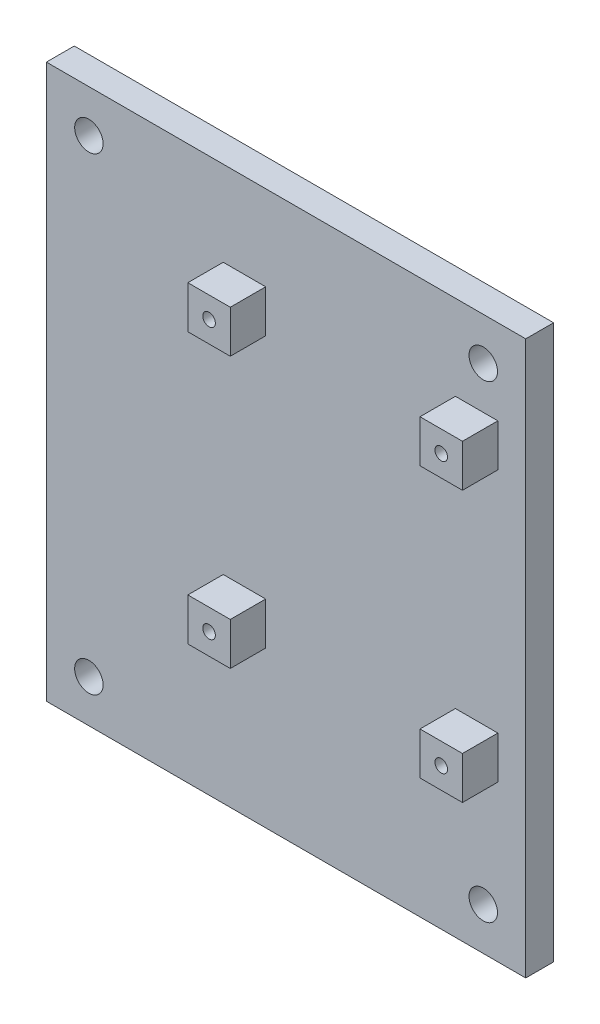
SolidWorks part; units mm, degrees
ref_plane "Front Plane" through (0, 0, 0) normal (0, 0, 1) x (1, 0, 0)
ref_plane "Top Plane" through (0, 0, 0) normal (0, 1, 0) x (1, 0, 0)
ref_plane "Right Plane" through (0, 0, 0) normal (1, 0, 0) x (0, 0, -1)
sketch "Sketch1" plane through (0, 0, 0) normal (0, 0, 1) x (1, 0, 0)
  line L1 (-43, -49.657) -> (43, -49.657)
  line L2 (-43, -49.657) -> (-43, 49.657)
  line L3 (-43, 49.657) -> (43, 49.657)
  line L4 (43, -49.657) -> (43, 49.657)
  line L5 (-43, -49.657) -> (43, 49.657) construction
  line L6 (-43, 49.657) -> (43, -49.657) construction
  point P0 (0, 0)
  dimension "D1" = 86
  dimension "D2" = 99.314
extrude "Boss-Extrude1" add sketch "Sketch1" along normal blind 5
sketch "Sketch2" plane through (0, 0, 5) normal (0, 0, 1) x (1, 0, 0)
  line L0 (43, 49.657) -> (-43, 49.657) construction
  line L1 (-11.276, 34.417) -> (-3.656, 34.417)
  line L2 (-11.276, 34.417) -> (-11.276, 26.797)
  line L3 (-11.276, 26.797) -> (-3.656, 26.797)
  line L4 (-3.656, 34.417) -> (-3.656, 26.797)
  line L5 (30.38, 34.417) -> (38, 34.417)
  line L6 (30.38, 34.417) -> (30.38, 26.797)
  line L7 (30.38, 26.797) -> (38, 26.797)
  line L8 (38, 34.417) -> (38, 26.797)
  line L9 (-11.276, -14.097) -> (-3.656, -14.097)
  line L10 (-11.276, -14.097) -> (-11.276, -21.717)
  line L11 (-11.276, -21.717) -> (-3.656, -21.717)
  line L12 (-3.656, -14.097) -> (-3.656, -21.717)
  line L13 (30.38, -14.097) -> (38, -14.097)
  line L14 (30.38, -14.097) -> (30.38, -21.717)
  line L15 (30.38, -21.717) -> (38, -21.717)
  line L16 (38, -14.097) -> (38, -21.717)
  line L18 (43, -49.657) -> (43, 49.657) construction
  dimension "D1" = 7.62
  dimension "D2" = 15.24
  dimension "D3" = 5
  dimension "D4" = 49.276
  dimension "D5" = 56.134
extrude "Boss-Extrude2" add sketch "Sketch2" along normal blind 6.35
hole_wizard "#4-40 Tapped Hole1" positions "Sketch3" profile "Sketch4" tap size "#4-40" standard "ANSI Inch"
sketch "Sketch3" plane through (0, 0, 11.35) normal (0, 0, 1) x (1, 0, 0)
  line L0 (-3.656, 34.417) -> (-11.276, 34.417) construction
  line L1 (-11.276, 34.417) -> (-11.276, 26.797) construction
  line L2 (38, 34.417) -> (30.38, 34.417) construction
  line L3 (30.38, 34.417) -> (30.38, 26.797) construction
  line L4 (-3.656, -14.097) -> (-11.276, -14.097) construction
  line L5 (-11.276, -14.097) -> (-11.276, -21.717) construction
  line L6 (38, -14.097) -> (30.38, -14.097) construction
  line L7 (30.38, -14.097) -> (30.38, -21.717) construction
  point P0 (-7.466, 30.607)
  point P2 (34.19, 30.607)
  point P4 (-7.466, -17.907)
  point P6 (34.19, -17.907)
  point P12 (-7.466, 34.417)
  point P16 (-11.276, 30.607)
  point P20 (34.19, 34.417)
  point P24 (30.38, 30.607)
  point P28 (-7.466, -14.097)
  point P32 (-11.276, -17.907)
  point P36 (34.19, -14.097)
  point P40 (30.38, -17.907)
sketch "Sketch4" plane through (-7.466, 30.607, 11.35) normal (1, 0, 0) x (0, -1, 0)
  line L0 (0, 0) -> (0, 5.429)
  line L1 (0, 5.429) -> (1.1303, 4.7498)
  line L2 (1.1303, 4.7498) -> (1.1303, 0)
  line L5 (1.1303, 0) -> (0, 0)
  line L10 (0, 5.429) -> (-1.1303, 4.7498) construction
  line L11 (0, -6.35) -> (0, 107.95) construction
  dimension "Tap Drill Dia." = 2.2606
  dimension "Tap Drill Depth" = 4.7498
  dimension "Drill Angle" = 118
cosmetic thread "Hole Thread1" parameters "D1"=5.588, "D2"=2.8448
cosmetic thread "Hole Thread2" parameters "D1"=5.588, "D2"=2.8448
cosmetic thread "Hole Thread3" parameters "D1"=5.588, "D2"=2.8448
cosmetic thread "Hole Thread4" parameters "D1"=5.588, "D2"=2.8448
hole_wizard "#10 Clearance Hole1" positions "Sketch5" profile "Sketch6" hole size "#10" standard "ANSI Inch" end condition through all
sketch "Sketch5" plane through (0, 0, 5) normal (0, 0, 1) x (1, 0, 0)
  line L0 (-43, 49.657) -> (-43, -49.657) construction
  line L1 (43, 49.657) -> (-43, 49.657) construction
  line L2 (43, -49.657) -> (43, 49.657) construction
  line L3 (-43, -49.657) -> (43, -49.657) construction
  point P0 (-35.38, 42.037)
  point P2 (35.38, 42.037)
  point P4 (-35.38, -42.037)
  point P6 (35.38, -42.037)
  dimension "D1" = 7.62
  dimension "D2" = 7.62
  dimension "D3" = 7.62
  dimension "D4" = 7.62
  dimension "D5" = 7.62
  dimension "D6" = 7.62
  dimension "D7" = 7.62
  dimension "D8" = 7.62
sketch "Sketch6" plane through (-35.38, 42.037, 5) normal (1, 0, 0) x (0, -1, 0)
  line L0 (0, 0) -> (0, 5)
  line L1 (0, 5) -> (2.5527, 5)
  line L2 (2.5527, 5) -> (2.5527, 0)
  line L5 (2.5527, 0) -> (0, 0)
  line L11 (0, -6.35) -> (0, 107.95) construction
  dimension "Thru Hole Dia." = 5.1054
  dimension "Thru Hole Depth" = 5
equation "\"PCB Width\"= 1940mil"
equation "\"PCB Height\"= 2210mil"
equation "\"PCB Thickness\"= 63mil"
equation "\"PCB Mount Height\"= 0.25in"
equation "\"Motor Body Front Diameter\"= 37mm"
equation "\"Motor Body Front Length\"= 30mm"
equation "\"Motor Bearing Length\"= 5mm"
equation "\"Motor Body Back Length\"= 33.3mm"
equation "\"Motor PCR\"= 31mm / 2"
equation "\"Large PVC Fittings Wall Thickness\"= 15in / 64"
equation "\"Large PVC Pipe Outer Diameter\"= 3.5in"
equation "\"Box Width\"= 2 * \"Motor Bearing Length\" + \"Motor Body Front Length\" + \"Motor Body Back Length\" + 0.5in"
equation "\"Box Hole Center to Edge Distance\"= 300mil"
equation "\"Box Ceiling and Floor Thickness\"= 2 * \"Box Hole Center to Edge Distance\""
equation "\"Box Height\"= 2 * \"Box Ceiling and Floor Thickness\" + \"PCB Height\" + 0.5in"
equation "\"Box Middle Depth\"= \"Large PVC Fittings Wall Thickness\" + \"Large PVC Pipe Outer Diameter\" / 2 + \"Motor Body Front Diameter\" / 2 - \"Motor Bearing Length\""
equation "\"D1@Sketch1\"=\"Box Width\" "
equation "\"D2@Sketch1\"=\"Box Height\""
equation "\"D1@Boss-Extrude1\"=\"Motor Bearing Length\""
equation "\"D2@Sketch2\"=\"Box Ceiling and Floor Thickness\""
equation "\"D3@Sketch2\"=\"Motor Bearing Length\""
equation "\"D4@Sketch2\"=\"PCB Width\""
equation "\"D5@Sketch2\"=\"PCB Height\""
equation "\"D1@Boss-Extrude2\"=\"PCB Mount Height\""
equation "\"Tap Drill Depth@Sketch4\"=0.25in - \"PCB Thickness\""
equation "\"D1@Sketch5\"=\"Box Hole Center to Edge Distance\""
equation "\"D2@Sketch5\"=\"Box Hole Center to Edge Distance\""
equation "\"D3@Sketch5\"=\"Box Hole Center to Edge Distance\""
equation "\"D4@Sketch5\"=\"Box Hole Center to Edge Distance\""
equation "\"D5@Sketch5\"=\"Box Hole Center to Edge Distance\""
equation "\"D6@Sketch5\"=\"Box Hole Center to Edge Distance\""
equation "\"D7@Sketch5\"=\"Box Hole Center to Edge Distance\""
equation "\"D8@Sketch5\"=\"Box Hole Center to Edge Distance\""
